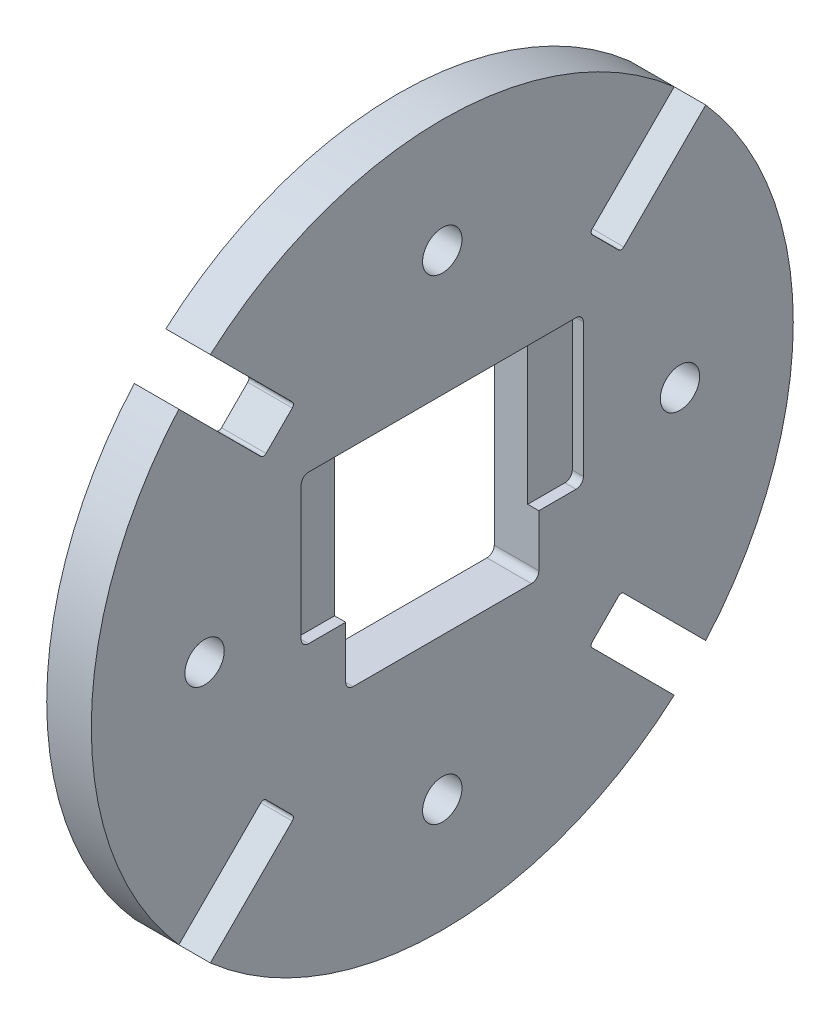
SolidWorks part; units mm, degrees
note: '?' marks a value the reader was unsure of.
material "Perspex (TM) GS Acrylic Cast Sheet"
ref_plane "Front Plane" through (0, 0, 0) normal (0, 0, 1) x (1, 0, 0)
ref_plane "Top Plane" through (0, 0, 0) normal (0, 1, 0) x (1, 0, 0)
ref_plane "Right Plane" through (0, 0, 0) normal (1, 0, 0) x (0, 0, -1)
sketch "Sketch1" plane through (0, 0, 0) normal (1, 0, 0) x (0, 0, -1)
  circle A0 centre (0, 0) radius 47.25
  dimension "D2" = 94.5
extrude "Boss-Extrude1" add sketch "Sketch1" along normal blind 6
sketch "Sketch2" plane through (6, 0, 0) normal (1, 0, 0) x (0, 0, -1)
  line L0 (12, -12.85) -> (-12, -12.85)
  line L1 (13, -3.85) -> (13, -11.85)
  line L2 (12, -11.85) -> (-12, -11.85)
  line L3 (-13, -11.85) -> (-13, -3.85)
  line L4 (-13, -3.85) -> (-13, 14.15)
  line L5 (13, -3.85) -> (13, 14.15)
  line L6 (12, 15.15) -> (-12, 15.15)
  line L7 (12, -12.85) -> (-12, -12.85) construction
  arc A0 (13, -11.85) -> (12, -12.85) centre (12, -11.85) cw
  arc A1 (-13, -11.85) -> (-12, -12.85) centre (-12, -11.85) ccw
  arc A4 (12, -11.85) -> (13, -10.85) centre (12, -10.85) ccw
  arc A5 (-13, -10.85) -> (-12, -11.85) centre (-12, -10.85) ccw
  arc A8 (-13, 14.15) -> (-12, 15.15) centre (-12, 14.15) cw
  arc A9 (13, 14.15) -> (12, 15.15) centre (12, 14.15) ccw
  point P26 (13, 15.15)
  dimension "D2" = 1
  dimension "D4" = 1
  dimension "D1" = 19
  dimension "D3" = 1
extrude "Cut-Extrude1" cut sketch "Sketch2" against normal blind 20 contours A5 L3 A1 L0 A0 L1 A4 L2 | L5 A9 L6 A8 L4 L3 A5 L2 A4 L1
sketch "Sketch3" plane through (6, 0, 0) normal (1, 0, 0) x (0, 0, -1)
  line L0 (0, 0) -> (-33.4108, 33.4108)
  line L1 (-33.4108, 33.4108) -> (33.4108, -33.4108)
  line L2 (0, 0) -> (33.4108, 33.4108)
  line L3 (0, 0) -> (-33.4108, -33.4108)
  circle A0 centre (0, 0) radius 47.25 construction
ref_plane "Plane1" through (0, 33.4108, 33.4108) normal (0, 0.7071, 0.7071) x (-1, 0, 0)
ref_plane "Plane2" through (0, -33.4108, 33.4108) normal (0, -0.7071, 0.7071) x (-1, 0, 0)
ref_plane "Plane3" through (0, 33.4108, -33.4108) normal (0, 0.7071, -0.7071) x (-1, 0, 0)
ref_plane "Plane4" through (0, -33.4108, -33.4108) normal (0, -0.7071, -0.7071) x (-1, 0, 0)
hole_wizard "Ø6.0mm Dowel Hole1" [suppressed] positions "Sketch5" profile "Sketch4" hole size "Ø6.0" standard "ISO"
sketch "Sketch5" plane through (0, 33.4108, 33.4108) normal (0, 0.7071, 0.7071) x (-1, 0, 0)
  line L0 (-6, 0) -> (-6, 47.25) construction
  point P0 (1.5, 0)
  dimension "D1" = 7.5
sketch "Sketch4" plane through (-1.5, 33.4108, 33.4108) normal (1, 0, 0) x (0, -0.7071, 0.7071)
  line L0 (0, 0) -> (0, 17.8026)
  line L1 (0, 17.8026) -> (3, 16)
  line L2 (3, 16) -> (3, 0)
  line L5 (3, 0) -> (0, 0)
  line L10 (0, 17.8026) -> (-3, 16) construction
  line L11 (0, -6.35) -> (0, 107.95) construction
  dimension "Hole Dia." = 6
  dimension "Hole Depth" = 16
  dimension "Drill Angle" = 118
hole_wizard "Ø6.0mm Dowel Hole2" [suppressed] positions "Sketch7" profile "Sketch6" hole size "Ø6.0" standard "ISO"
sketch "Sketch7" plane through (0, -33.4108, 33.4108) normal (0, -0.7071, 0.7071) x (-1, 0, 0)
  line L0 (-6, 0) -> (-6, -47.25) construction
  point P0 (1.5, 0)
  dimension "D1" = 7.5
sketch "Sketch6" plane through (-1.5, -33.4108, 33.4108) normal (1, 0, 0) x (0, -0.7071, -0.7071)
  line L0 (0, 0) -> (0, 17.8026)
  line L1 (0, 17.8026) -> (3, 16)
  line L2 (3, 16) -> (3, 0)
  line L5 (3, 0) -> (0, 0)
  line L10 (0, 17.8026) -> (-3, 16) construction
  line L11 (0, -6.35) -> (0, 107.95) construction
  dimension "Hole Dia." = 6
  dimension "Hole Depth" = 16
  dimension "Drill Angle" = 118
hole_wizard "Ø6.0mm Dowel Hole3" [suppressed] positions "Sketch9" profile "Sketch8" hole size "Ø6.0" standard "ISO"
sketch "Sketch9" plane through (0, -33.4108, -33.4108) normal (0, -0.7071, -0.7071) x (-1, 0, 0)
  line L0 (-6, 0) -> (-6, -47.25) construction
  point P0 (1.5, 0)
  dimension "D1" = 7.5
sketch "Sketch8" plane through (-1.5, -33.4108, -33.4108) normal (1, 0, 0) x (0, 0.7071, -0.7071)
  line L0 (0, 0) -> (0, 17.8026)
  line L1 (0, 17.8026) -> (3, 16)
  line L2 (3, 16) -> (3, 0)
  line L5 (3, 0) -> (0, 0)
  line L10 (0, 17.8026) -> (-3, 16) construction
  line L11 (0, -6.35) -> (0, 107.95) construction
  dimension "Hole Dia." = 6
  dimension "Hole Depth" = 16
  dimension "Drill Angle" = 118
hole_wizard "Ø6.0mm Dowel Hole4" [suppressed] positions "Sketch11" profile "Sketch10" hole size "Ø6.0" standard "ISO"
sketch "Sketch11" plane through (0, 33.4108, -33.4108) normal (0, 0.7071, -0.7071) x (-1, 0, 0)
  line L0 (0, -47.25) -> (0, 47.25) construction
  point P0 (-7.5, 0)
  dimension "D1" = 7.5
sketch "Sketch10" plane through (7.5, 33.4108, -33.4108) normal (1, 0, 0) x (0, 0.7071, 0.7071)
  line L0 (0, 0) -> (0, 17.8026)
  line L1 (0, 17.8026) -> (3, 16)
  line L2 (3, 16) -> (3, 0)
  line L5 (3, 0) -> (0, 0)
  line L10 (0, 17.8026) -> (-3, 16) construction
  line L11 (0, -6.35) -> (0, 107.95) construction
  dimension "Hole Dia." = 6
  dimension "Hole Depth" = 16
  dimension "Drill Angle" = 118
hole_wizard "M5 Clearance Hole1" positions "Sketch15" profile "Sketch14" hole size "M5" standard "ISO"
sketch "Sketch15" plane through (0, 0, 0) normal (-1, 0, 0) x (0, 0, 1)
  point P0 (-32, 0)
  point P8 (0, 32)
  point P9 (32, 0)
  point P10 (0, -32)
  dimension "D2" = 4
sketch "Sketch14" plane through (0, 0, -32) normal (0, 1, 0) x (0, 0, 1)
  line L0 (0, 0) -> (0, 17.5923)
  line L1 (0, 17.5923) -> (2.65, 16)
  line L2 (2.65, 16) -> (2.65, 0)
  line L5 (2.65, 0) -> (0, 0)
  line L10 (0, 17.5923) -> (-2.65, 16) construction
  line L11 (0, -6.35) -> (0, 107.95) construction
  dimension "Hole Dia." = 5.3
  dimension "Hole Depth" = 16
  dimension "Drill Angle" = 118
sketch "Sketch16" plane through (6, 0, 0) normal (1, 0, 0) x (0, 0, -1)
  line L0 (12, 15.15) -> (-12, 15.15) construction
  line L1 (19, 15.15) -> (-19, 15.15)
  line L2 (0, 15.15) -> (0, -4.85)
  line L3 (19, -4.85) -> (-19, -4.85)
  line L4 (-19, 15.15) -> (-19, -4.85)
  line L5 (19, 15.15) -> (19, -4.85)
  line M5 (13, 14.15) -> (13, -11.85)
  line M9 (-13, -11.85) -> (-13, 14.15)
  arc M10 (-13, 14.15) -> (-12, 15.15) centre (-12, 14.15) cw
  line M11 (-12, 15.15) -> (12, 15.15)
  arc M12 (12, 15.15) -> (13, 14.15) centre (12, 14.15) cw
  dimension "D1" = 19
  dimension "D2" = 20
extrude "Cut-Extrude2" cut sketch "Sketch16" against normal blind 1.5 contours L5 L1 L3 M12 M5 | L3 L1 L2 M5 M12 | L3 L2 M11 M10 M9 | L1 L4 L3 M9 M10
fillet "Fillet1" radius 1 4 edges at (5.25, -4.85, -19) (5.25, -4.85, 19) (5.25, 15.15, 19) (5.25, 15.15, -19)
ref_axis "Axis1" through (6, 0, 0) along (-1, 0, 0)?
sketch "Sketch17" plane through (6, 0, 0) normal (1, 0, 0) x (0, 0, -1)
  line L0 (0, 0) -> (33.4108, -33.4108)
  line L1 (-5.4801, -72.3017) -> (72.3017, 5.4801) construction
  line L2 (20.1879, -24.4305) -> (31.2895, -35.5321)
  line L3 (24.4305, -20.1879) -> (35.5321, -31.2895)
  line L4 (35.5321, -31.2895) -> (31.2895, -35.5321)
  line L5 (23.7234, -20.1879) -> (20.1879, -23.7234)
  line L6 (-2.1213, -2.1213) -> (31.2895, -35.5321) construction
  line L7 (2.1213, 2.1213) -> (35.5321, -31.2895) construction
  line L8 (-24.4305, -20.1879) -> (-35.5321, -31.2895)
  line L9 (0, 0) -> (-33.4108, -33.4108)
  line L10 (-20.1879, -24.4305) -> (-31.2895, -35.5321)
  line L11 (-20.1879, -23.7234) -> (-23.7234, -20.1879)
  line L12 (-31.2895, -35.5321) -> (-35.5321, -31.2895)
  line L13 (-20.1879, 24.4305) -> (-31.2895, 35.5321)
  line L14 (0, 0) -> (-33.4108, 33.4108)
  line L15 (-24.4305, 20.1879) -> (-35.5321, 31.2895)
  line L16 (-23.7234, 20.1879) -> (-20.1879, 23.7234)
  line L17 (-35.5321, 31.2895) -> (-31.2895, 35.5321)
  line L18 (24.4305, 20.1879) -> (35.5321, 31.2895)
  line L19 (0, 0) -> (33.4108, 33.4108)
  line L20 (20.1879, 24.4305) -> (31.2895, 35.5321)
  line L21 (20.1879, 23.7234) -> (23.7234, 20.1879)
  line L22 (31.2895, 35.5321) -> (35.5321, 31.2895)
  arc A1 (23.7234, -20.1879) -> (24.4305, -20.1879) centre (24.077, -20.5415) cw
  arc A2 (20.1879, -23.7234) -> (20.1879, -24.4305) centre (20.5415, -24.077) ccw
  arc A3 (-20.1879, -23.7234) -> (-20.1879, -24.4305) centre (-20.5415, -24.077) cw
  arc A4 (-23.7234, -20.1879) -> (-24.4305, -20.1879) centre (-24.077, -20.5415) ccw
  arc A5 (-23.7234, 20.1879) -> (-24.4305, 20.1879) centre (-24.077, 20.5415) cw
  arc A6 (-20.1879, 23.7234) -> (-20.1879, 24.4305) centre (-20.5415, 24.077) ccw
  arc A7 (20.1879, 23.7234) -> (20.1879, 24.4305) centre (20.5415, 24.077) cw
  arc A8 (23.7234, 20.1879) -> (24.4305, 20.1879) centre (24.077, 20.5415) ccw
  point P44 (0, 0)
  circle M21 centre (0, 0) radius 47.25
  dimension "D1" = 3
  dimension "D4" = 0.5
  dimension "D3" = 16.2
  dimension "D2" = 3
extrude "Cut-Extrude3" cut sketch "Sketch17" against normal blind 10 contours A3 L11 L9 L10 M21 | L11 A4 L8 L9 M21 | L5 A2 L2 L0 M21 | A1 L5 L0 L3 M21 | A7 L21 L19 L20 M21 | L21 A8 L18 L19 M21 | A5 L16 L14 L15 M21 | L16 A6 L13 L14 M21
